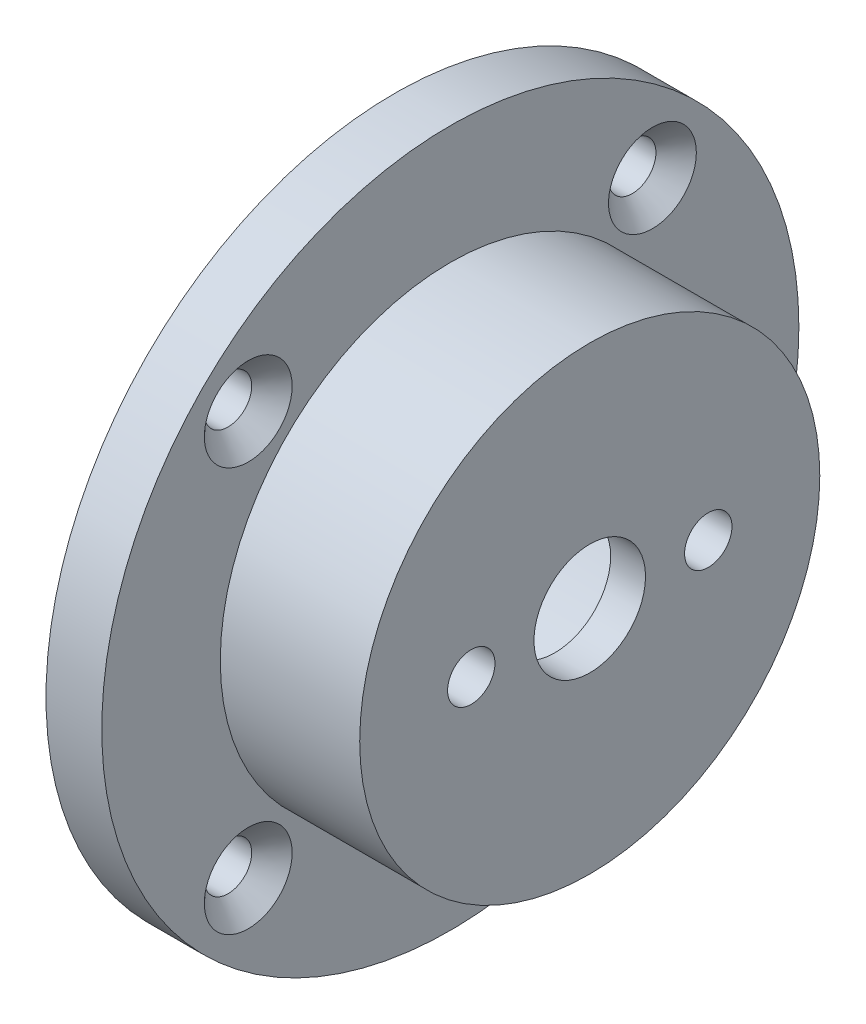
SolidWorks part; units mm, degrees
material "ABS"
ref_plane "Front Plane" through (0, 0, 0) normal (0, 0, 1) x (1, 0, 0)
ref_plane "Top Plane" through (0, 0, 0) normal (0, 1, 0) x (1, 0, 0)
ref_plane "Right Plane" through (0, 0, 0) normal (1, 0, 0) x (0, 0, -1)
sketch "Sketch1" plane through (0, 0, 0) normal (1, 0, 0) x (0, 0, -1)
  circle A0 centre (0, 0) radius 25
extrude "Boss-Extrude1" add sketch "Sketch1" along normal blind 4
sketch "Sketch2" plane through (4, 0, 0) normal (1, 0, 0) x (0, 0, -1)
  circle A0 centre (0, 0) radius 16.5
extrude "Boss-Extrude2" add sketch "Sketch2" along normal blind 10
sketch "Sketch3" plane through (0, 0, 0) normal (-1, 0, 0) x (0, 0, 1)
  circle A0 centre (0, 0) radius 12.5
extrude "Cut-Extrude1" cut sketch "Sketch3" against normal offset from surface (11.5 mm away) 2.5 up to face at (14, 0, -16.5)
sketch "Sketch4" plane through (14, 0, 0) normal (1, 0, 0) x (0, 0, -1)
  circle A0 centre (0, 0) radius 4
extrude "Cut-Extrude2" cut sketch "Sketch4" against normal blind 4
hole_wizard "M3 Clearance Hole1" positions "Sketch6" profile "Sketch5" hole size "M3" standard "ANSI Metric"
sketch "Sketch6" plane through (14, 0, 0) normal (1, 0, 0) x (0, 0, -1)
  point P0 (8.5, 0)
  point P2 (-8.5, 0)
  dimension "D1" = 8.5
  dimension "D2" = 8.5
sketch "Sketch5" plane through (14, 0, -8.5) normal (0, 1, 0) x (0, 0, -1)
  line L0 (0, 0) -> (0, 10)
  line L1 (0, 10) -> (1.7, 10)
  line L2 (1.7, 10) -> (1.7, 0)
  line L5 (1.7, 0) -> (0, 0)
  line L10 (0, 10) -> (-1.7, 10) construction
  line L11 (0, -6.35) -> (0, 107.95) construction
  dimension "Hole Dia." = 3.4
  dimension "Hole Depth" = 10
  dimension "Drill Angle" = 180
sketch "Sketch7" plane through (4, 0, 0) normal (1, 0, 0) x (0, 0, -1)
  line L0 (0, 0) -> (-14.4957, -14.4957) construction
hole_wizard "CSK for M3 Flat Head Machine Screw1" positions "Sketch9" profile "Sketch8" countersink size "M3" standard "ANSI Metric" end condition through all
sketch "Sketch9" plane through (4, 0, 0) normal (1, 0, 0) x (0, 0, -1)
  point P0 (-14.4957, -14.4957)
sketch "Sketch8" plane through (4, -14.4957, 14.4957) normal (0, 1, 0) x (0, 0, -1)
  line L0 (0, 0) -> (0, 4)
  line L1 (0, 4) -> (1.7, 4)
  line L2 (1.7, 4) -> (1.7, 1.45)
  line L3 (1.7, 1.45) -> (3.15, 0)
  line L5 (3.15, 0) -> (0, 0)
  line L6 (-1.7, 1.45) -> (-3.15, 0) construction
  line L11 (0, -6.35) -> (0, 107.95) construction
  dimension "Thru Hole Dia." = 3.4
  dimension "Thru Hole Depth" = 4
  dimension "Near C'Sink Dia." = 6.3
  dimension "Near C'Sink Angle" = 90
pattern_circular "CirPattern1" count 4 over 360 about axis through (14, 0, 0) along (1, 0, 0) of "CSK for M3 Flat Head Machine Screw1"
sketch "Sketch10" plane through (0, 0, 0) normal (-1, 0, 0) x (0, 0, 1)
  circle A0 centre (0, 0) radius 13.125
extrude "Cut-Extrude3" cut sketch "Sketch10" against normal up to surface (11.5 mm away) up to face at (11.5, 0, -10.2)
